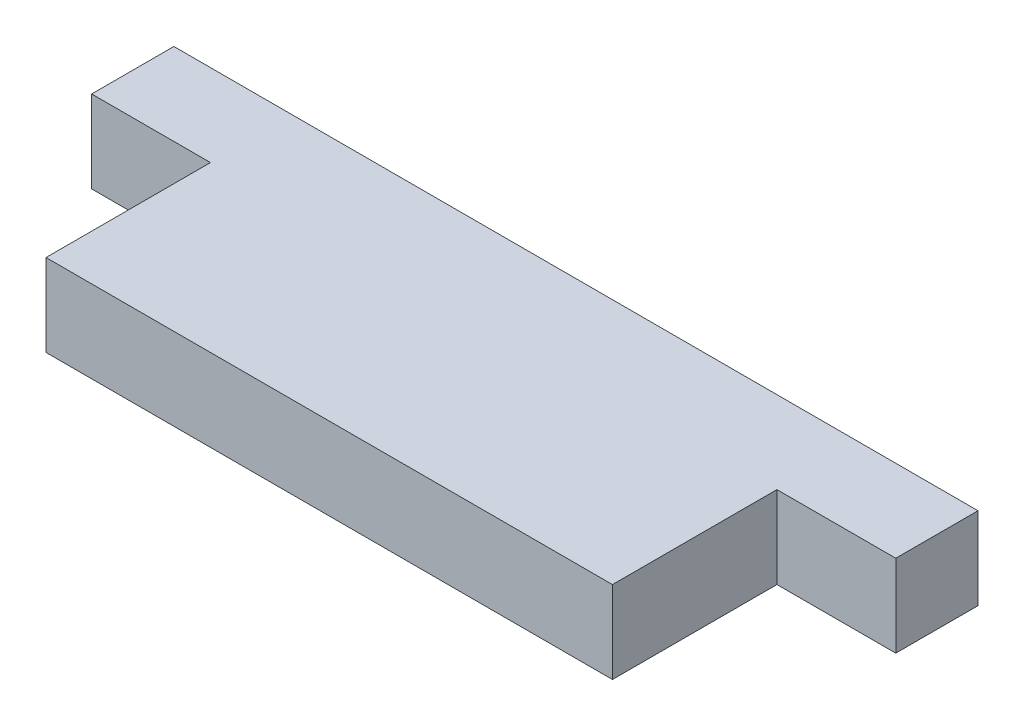
SolidWorks part; units mm, degrees
material "Beech"
ref_plane "Front Plane" through (0, 0, 0) normal (0, 0, 1) x (1, 0, 0)
ref_plane "Top Plane" through (0, 0, 0) normal (0, 1, 0) x (1, 0, 0)
ref_plane "Right Plane" through (0, 0, 0) normal (1, 0, 0) x (0, 0, -1)
sketch "Sketch1" plane through (0, 0, 0) normal (0, 1, 0) x (1, 0, 0)
  line L0 (0, 0) -> (0, 12.7)
  line L1 (0, 0) -> (43.74, 0)
  line L3 (43.74, 0) -> (43.74, 12.7)
  line L4 (-9.1751, 19.05) -> (52.9151, 19.05)
  line L5 (-9.1751, 19.05) -> (-9.1751, 12.7)
  line L6 (52.9151, 19.05) -> (52.9151, 12.7)
  line L7 (-9.1751, 12.7) -> (0, 12.7)
  line L8 (43.74, 12.7) -> (52.9151, 12.7)
  dimension "D1" = 12.7
  dimension "D2" = 43.74
  dimension "D3" = 6.35
  dimension "D4" = 9.1751
  dimension "D5" = 9.1751
extrude "Boss-Extrude1" add sketch "Sketch1" along normal blind 6.35
equation "\"MotorMountLegLength\"=.25in"
equation "\"GearOffset\"=.264907in"
equation "\"D4@Sketch1\"=\"TriggerRackOffset\"+.125in"
equation "\"D5@Sketch1\"=\"TriggerRackOffset\"+.125in"
equation "\"D2@Sketch1\" = \"CageLeftBottomEdge\" + \"CageRightBottomEdge\""
equation "\"CageLeftBottomEdge\"=22.11mm"
equation "\"CageLeftTopEdge\"=22.11mm"
equation "\"CageRightBottomEdge\"=21.63mm"
equation "\"CageRightTopEdge\"=21.63mm"
equation "\"CageHeight\"=86.04mm"
equation "\"CageLength\"=73.76mm"
equation "\"CageTopScrewClearance\"=10mm"
equation "\"CageBottomScrewClearance\"=25mm"
equation "\"CageLeftTopDepth\"= 11.65mm"
equation "\"CageLeftBottomDepth\"=11.11mm"
equation "\"CageLeftTopHeight\"=8.56175mm"
equation "\"CageLeftBottomHeight\"=16mm"
equation "\"CageRightTopDepth\"= 11.05mm"
equation "\"CageRightBottomDepth\"=10.58mm"
equation "\"CageRightTopHeight\"=9.6mm"
equation "\"CageRightBottomHeight\"=15.49mm"
equation "\"CageLeftTopChannelDepth\"=2.41908mm"
equation "\"CageLeftBottomChannelDepth\"=2.588mm"
equation "\"CageLeftChannelHeight\"=11.7mm"
equation "\"CageRightTopChannelDepth\"=2.32mm"
equation "\"CageRightBottomChannelDepth\"=2.318mm"
equation "\"CageRightChannelHeight\"=10mm"
equation "\"CageChanRelHeight\"=23.99mm"
equation "\"CageChanRelDepth\"=5.492mm"
equation "\"CageChamberRadius\"=16.261mm"
equation "\"CageScrewDiameter\"=4.8mm"
equation "\"CageSetScrewDiameter\"=3.5mm"
equation "\"CageAxleRadius\"=6.639mm"
equation "\"CageAxleKeyHeight\"=1.619mm"
equation "\"CageAxleKeyWidth\"=2.662mm"
equation "\"CageHoseWindowWidth\"=16.29mm"
equation "\"CageHoseWindowHeight\"=26.5mm"
equation "\"CageHoseWindow-Edge\"=8.89mm"
equation "\"CageScrew-VerticalEdge\"=5.0mm"
equation "\"CageScrew-HorizontalEdge\"=7.5mm"
equation "\"CageScrew-HoseCornerScrewEdge\"=4.45mm"
equation "\"CageAxle-BottomEdge\"=56.05mm"
equation "\"CageAxle-FrontEdge\"=46.03mm"
equation "\"CageBackSetScrew-Axle\"=40mm"
equation "\"CageFrontSetScrew-Axle\"=22mm"
equation "\"CageVelocityWindow-BackEdge\"=34.8mm"
equation "\"CageVelocityWindow-BottomEdge\"=27.55mm"
equation "\"CageVelocityWindowHeight\"=22.29mm"
equation "\"CageVelocityWindowWidth\"=12.61mm"
equation "\"TriggerSlot-BottomEdge\"=6.35mm"
equation "\"TriggerSlot-FrontEdge\"=15mm"
equation "\"TriggerSlotSize\"=6.7mm"
equation "\"TriggerRackOffset\"=.236224in"
equation "\"TriggerSlotSizeInt\"=.25in"
equation "\"TriggerSlotSpacing\"=.25in"
equation "\"TriggerMiniSlotWidth\"=3.5mm"
equation "\"TriggerRackWidth\"=6.5mm"
equation "\"whitemotordepth\"=11.27mm"
equation "\"whitemotorbackdepth\"=3.845mm"
equation "\"whitemotoraxledepth\" = 3.5mm"
equation "\"whitemotoraxleoffset\"=11.4mm"
equation "\"whitemotorwidth\"=12.07mm"
equation "\"whitemotorheight\"=16.68mm"
equation "\"whitemotorcylinderlength\" =13.04mm"
equation "\"whitemotorcylinderradius\"=3.845mm"
equation "\"whitemotorcylinderoffset\"=2.35mm"
equation "\"whitemotorcutoutlength\"=1.88mm"
equation "\"whitemotorouterrad\"=5mm"
equation "\"whitemotorinnerrad\"=2.95mm"
equation "\"elasticracklength\"=2in"
equation "\"elasticrackpegsize\"=.25in"
equation "\"elasticrackpegbuffer\"=.125in"
equation "\"elasticrackpegspacing\"=1.76476378in"
equation "\"elasticbaybuffer\"=.25in"
equation "\"elasticdepth\"=.125in"
equation "\"elasticbaydepth\"=.75in"
equation "\"motormountwidth\"=12mm"
equation "\"motormountcornerfillet\"=3mm"
equation "\"pandiscradius\"=14in"
equation "\"towermaterialwidth\"=.25in"
equation "\"towerslotlength\"=.5in"
equation "\"towermarkerspace\"=5in"
equation "\"towerslothorizoffset\"=1in"
equation "\"towerslothorizspacing\"=2in"
equation "\"towerslotvertoffset\"=3in"
equation "\"towerslotvertspacing\"=1in"
equation "\"towerheight\"=12in"
equation "\"towerupslot\"=1in"
equation "\"toweraxle\"=.5in"
equation "\"stepperouterrad\"=10mm"
equation "\"stepperscrewsize\"=3.45mm"
equation "\"stepperscrewc2c\"=49.5mm"
equation "\"stepperdepthoffset\"=24mm"
equation "\"stepperhorizoffset\"=22.91mm"
equation "\"shaftslotOD\"=18.8mm"
equation "\"shaftslotID\"=13.28mm"
equation "\"shaftkeywidth\"=2.67mm"
equation "\"shaftkeydepth\"=1.8mm"
equation "\"shaftcollartotaldepth\"=12.5mm"
equation "\"shaftsquaredepth\"=6mm"
equation "\"shaftsetscrewsize\"=3.5mm"
equation "\"shaftkeytightdepth\"=1.85mm"
equation "\"shaftslottightID\"=12.78mm"
equation "\"shaftsetscrewoffset\"=9mm"
equation "\"cagecollartotaldepth\"=10mm"
equation "\"cagecollartotalwidth\"=35mm"
equation "\"cagecollarbasedepth\"=4mm"
equation "\"gearhubintdiam\"=30mm"
equation "\"gearhubintwid\"=15mm"
equation "\"towerspeedwidth\"=2in"
equation "\"towerspeedheight\"=8in"
equation "\"towerspeedgap\"=2in"
equation "\"stepperaxleflat\"=.037in"
equation "\"stepperaxlerad\"=0.11811024in"
equation "\"ajaxaxlesize\"=3.87mm"
equation "\"ajaxinnercut\"=2.3mm"
equation "\"ajaxwidth\"=6.1mm"
equation "\"ajaxdiametral\"=25.8854"
equation "\"ajaxcutoutdepth\"=2.3mm"
equation "\"ajax4020gap\"=29.5mm"
equation "\"ajax4010gap\"=24.5mm"
equation "\"ajax20hubbuffer\"=6.1mm"
equation "\"ajax20hubholeoffset\"=.19685in"
equation "\"ajax20hubholesize\"=.059055in"
equation "\"ajax20cutoutint\"=13.4mm"
equation "\"ajax40hubholesize\"=7.21mm"
equation "\"ajax40hubholeoffset\"=10mm"
equation "\"ajax40hubbuffer\"=8.9mm"
equation "\"ajax40cutoutint\"=32.6mm"
equation "\"bearingpandiscrad\"=6.8in"
equation "\"bearingpandiscang\"=48.75deg"
equation "\"bearingclearholedist\"=4.7345in"
equation "\"bearingclearholesize\"=.5in"
equation "\"bearingclearholeang\"=22.5deg"
equation "\"bearingmountholedist\"=4.25in"
equation "\"bearingwirehole\"=1.5in"
equation "\"no6diam\"=.146in"
equation "\"shortconangle\"=20deg"
equation "\"shortconlen\"=.875in"
equation "\"longconlen\"=1.25in"
equation "\"longconangle\"=15deg"
